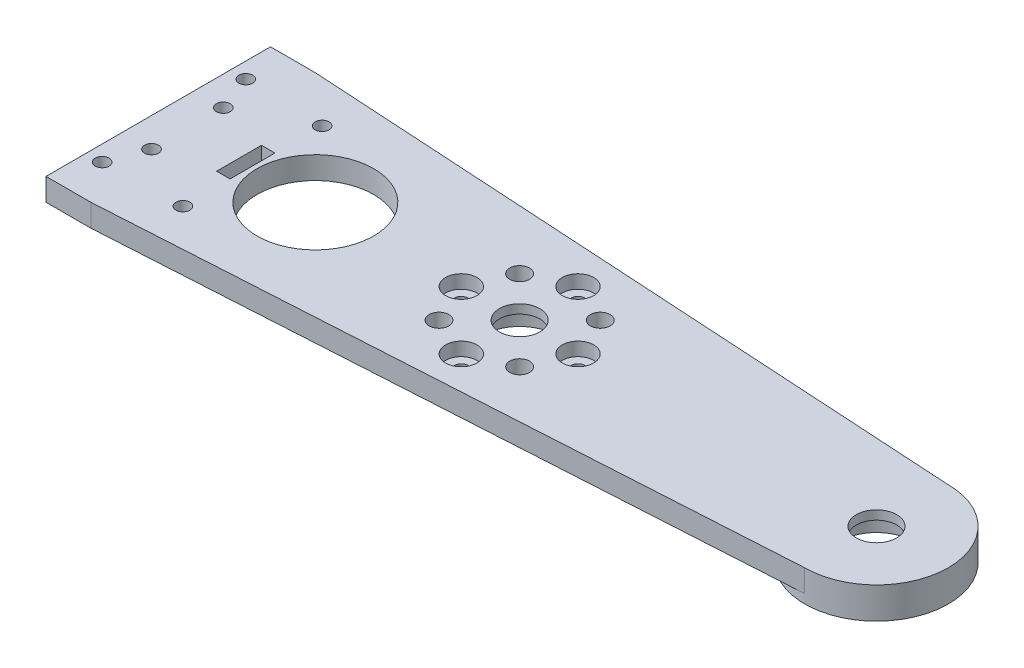
SolidWorks part; units mm, degrees
ref_plane "Front Plane" through (0, 0, 0) normal (0, 0, 1) x (1, 0, 0)
ref_plane "Top Plane" through (0, 0, 0) normal (0, 1, 0) x (1, 0, 0)
ref_plane "Right Plane" through (0, 0, 0) normal (1, 0, 0) x (0, 0, -1)
sketch "Sketch28" plane through (-32, 0, 0) normal (0, -1, 0) x (0, 0, 1)
  line L1 (0, -20) -> (0, -65.5) construction
  line L2 (-8, 8.5) -> (8, 8.5) construction
  line L3 (0, 15) -> (0, -3) construction
  line L8 (-25, 15) -> (25, 15)
  line L12 (25, 15) -> (25, 5)
  line L13 (-25, 15) -> (-25, 5)
  line L14 (-25, 5) -> (-16, -145)
  line L15 (16, -145) -> (25, 5)
  line L16 (-25, 5) -> (-25, 8.5) construction
  line L17 (-25, 8.5) -> (-8, 8.5) construction
  line L18 (-25, 15) -> (-25, 11.5) construction
  line L19 (-25, 11.5) -> (-16, 11.5) construction
  line L20 (-16, 11.5) -> (16, 11.5) construction
  line L21 (-5, -3) -> (5, -3)
  line L26 (5, -3) -> (5, -6)
  line L27 (5, -6) -> (-5, -6)
  line L28 (-5, -6) -> (-5, -3)
  line L29 (-5, -3) -> (-15.5, -3) construction
  line L30 (-15.5, -3) -> (-15.5, -6) construction
  line L31 (5, -3) -> (15.5, -3) construction
  line L32 (15.5, -3) -> (15.5, -6) construction
  line L33 (0, -20) -> (0, -6) construction
  line L34 (0, -65.5) -> (0, -145) construction
  circle A7 centre (8, 8.5) radius 1.55
  circle A8 centre (-8, 8.5) radius 1.55
  circle A9 centre (16, 11.5) radius 1.55
  circle A10 centre (-16, 11.5) radius 1.55
  circle A13 centre (-15.5, -6) radius 1.55
  circle A14 centre (15.5, -6) radius 1.55
  circle A15 centre (0, -20) radius 12.5 construction
  arc A17 (-16, -145) -> (16, -145) centre (0, -145) ccw
  circle A18 centre (0, -20) radius 13
  circle A19 centre (0, -145) radius 4.5
  circle A20 centre (0, -65.5) radius 4.5
  point P13 (0, 15)
  point P27 (0, -3)
extrude "Boss-Extrude10" add sketch "Sketch28" along normal blind 5
sketch "Sketch29" plane through (0, -5, 0) normal (0, -1, 0) x (1, 0, 0)
  circle A0 centre (113, 0) radius 16
  circle A2 centre (33.5, 0) radius 16
extrude "Boss-Extrude11" add sketch "Sketch29" along normal blind 2
sketch "Sketch30" plane through (0, -7, 0) normal (0, -1, 0) x (1, 0, 0)
  circle A0 centre (33.5, 0) radius 8.2
  circle A1 centre (113, 0) radius 8.2
extrude "Cut-Extrude1" cut sketch "Sketch30" against normal blind 5
sketch "Sketch31" plane through (0, -7, 0) normal (0, -1, 0) x (1, 0, 0)
  line L0 (33.5, 0) -> (42.4803, 8.9803) construction
  circle A0 centre (33.5, 0) radius 12.7 construction
  circle A1 centre (42.4803, 8.9803) radius 1.2
  circle A2 centre (42.4803, -8.9803) radius 1.2
  circle A3 centre (24.5197, -8.9803) radius 1.2
  circle A4 centre (24.5197, 8.9803) radius 1.2
  circle A5 centre (33.5, 0) radius 13 construction
  circle A6 centre (33.5, 13) radius 1.55
  circle A7 centre (46.5, 0) radius 1.55
  circle A8 centre (33.5, -13) radius 1.55
  circle A9 centre (20.5, 0) radius 1.55
  point P14 (33.5, 0)
  point P24 (33.5, 0)
  dimension "D1" = 4
  dimension "D2" = 4
extrude "Cut-Extrude2" cut sketch "Sketch31" against normal up to surface (7 mm away) up to face at (-43.5, 0, -17.55)
sketch "Sketch32" plane through (0, 0, 0) normal (0, 1, 0) x (1, 0, 0)
  circle A0 centre (33.5, 13) radius 3.5
  circle A1 centre (20.5, 0) radius 3.5
  circle A2 centre (33.5, -13) radius 3.5
  circle A3 centre (46.5, 0) radius 3.5
  point P12 (33.5, 0)
  point P22 (33.5, 0)
  dimension "D1" = 4
extrude "Cut-Extrude3" cut sketch "Sketch32" against normal blind 3
sketch "Sketch33" plane through (0, 0, 0) normal (0, 1, 0) x (1, 0, 0)
  circle A0 centre (24.5197, 8.9803) radius 2.2
  circle A1 centre (42.4803, 8.9803) radius 2.2
  circle A2 centre (42.4803, -8.9803) radius 2.2
  circle A3 centre (24.5197, -8.9803) radius 2.2
  point P12 (33.5, 0)
extrude "Cut-Extrude4" cut sketch "Sketch33" against normal blind 5
